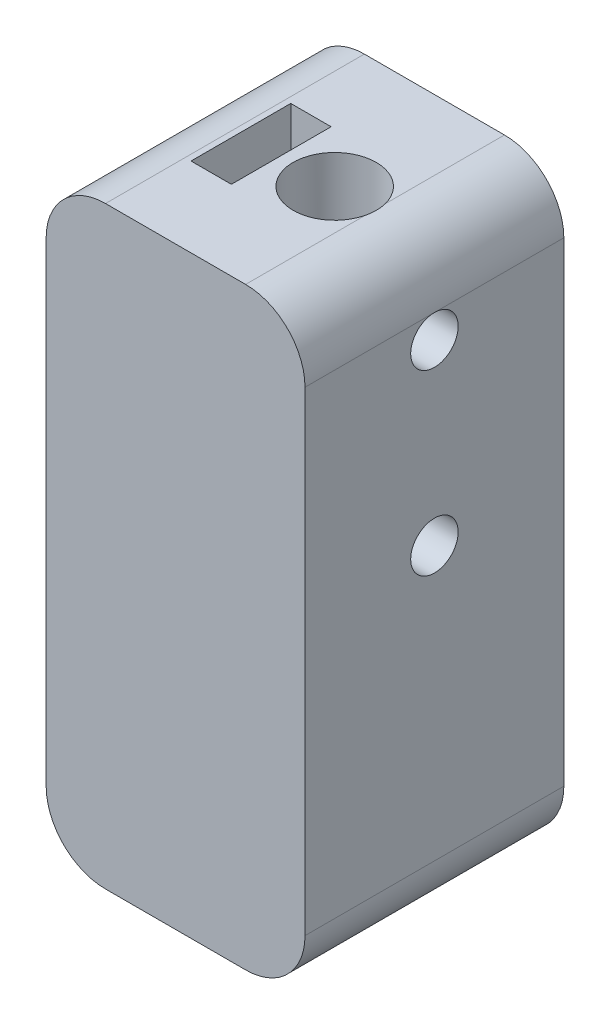
SolidWorks part; units mm, degrees
ref_plane "Alzado" through (0, 0, 0) normal (0, 0, 1) x (1, 0, 0)
ref_plane "Planta" through (0, 0, 0) normal (0, 1, 0) x (1, 0, 0)
ref_plane "Vista lateral" through (0, 0, 0) normal (1, 0, 0) x (0, 0, -1)
sketch "Croquis1" plane through (0, 0, 0) normal (1, 0, 0) x (0, 0, -1)
  line L1 (0, 0) -> (-21.8, 0)
  line L2 (0, 0) -> (0, -50)
  line L3 (0, -50) -> (-21.8, -50)
  line L4 (-21.8, 0) -> (-21.8, -50)
  dimension "D1" = 21.8
  dimension "D2" = 50
extrude "Saliente-Extruir1" add sketch "Croquis1" along normal blind 21.8 contours L2 L3 L4 L1
sketch "Croquis6" plane through (0, 0, 0) normal (-1, 0, 0) x (0, 0, 1)
  line L1 (10.9, -7) -> (10.9, 0) construction
  line L2 (10.9, -22) -> (10.9, -7) construction
  line L3 (0, 0) -> (21.8, 0) construction
  circle A0 centre (10.9, -22) radius 2
  circle A1 centre (10.9, -7) radius 2
  dimension "D1" = 15
  dimension "D3" = 4
  dimension "D4" = 4
  dimension "D2" = 7
extrude "Cortar-Extruir2" cut sketch "Croquis6" against normal up to surface (21.8 mm away) up to face at (21.8, -25, 10.9)
sketch "Croquis7" plane through (21.8, 0, 0) normal (1, 0, 0) x (0, 0, -1)
  line L2 (-10.9, -22) -> (-10.9, -7) construction
  circle A0 centre (-10.9, -22) radius 3.5
  circle A1 centre (-10.9, -7) radius 3.5
  circle A2 centre (-10.9, -7) radius 2 construction
  dimension "D1" = 7
  dimension "D2" = 7
  dimension "D3" = 15
sketch "Croquis11" plane through (0, -50, 0) normal (0, -1, 0) x (1, 0, 0)
  line L0 (13.4, 5.9) -> (13.4, 10.9) construction
  line L1 (0, 0) -> (0, 21.8) construction
  line L2 (0, 0) -> (0, 21.8) construction
  line L7 (16.9, 10.9) -> (21.8, 10.9) construction
  line L8 (13.4, 10.9) -> (8.9, 10.9) construction
  line L9 (8.9, 15.1) -> (5.5, 15.1)
  line L14 (8.9, 15.1) -> (8.9, 6.7)
  line L16 (8.9, 6.7) -> (5.5, 6.7)
  line L17 (5.5, 15.1) -> (5.5, 6.7)
  line L18 (21.8, 0) -> (21.8, 21.8) construction
  line L19 (5.5, 10.9) -> (0, 10.9) construction
  circle A1 centre (13.4, 10.9) radius 3.5
  dimension "D1" = 8.4
  dimension "D2" = 5.5
  dimension "D3" = 5
  dimension "D4" = 3.4
  dimension "D5" = 4.5
extrude "Cortar-Extruir4" cut sketch "Croquis11" against normal up to next
fillet "Redondeo1" radius 5 4 edges at (21.8, -50, 10.9) (0, -50, 10.9) (21.8, 0, 10.9) (0, 0, 10.9)
sketch "Croquis13" plane through (0, 0, 0) normal (-1, 0, 0) x (0, 0, 1)
  line L0 (10.9, -7) -> (10.9, -22) construction
  line L1 (10.9, -14.5) -> (2.8317, -14.5) construction
  circle A0 centre (10.9, -22) radius 2 construction
  circle A1 centre (10.9, -7) radius 2 construction
  circle A2 centre (10.9, -22) radius 2 construction
  circle A3 centre (10.9, -7) radius 2 construction
  circle A4 centre (10.9, -7) radius 3.5
  circle A5 centre (10.9, -22) radius 3.5
  dimension "D1" = 7
extrude "Cortar-Extruir6" cut sketch "Croquis13" against normal blind 3.5
sketch "Croquis15" plane through (0, -50, 0) normal (0, -1, 0) x (1, 0, 0)
  line L0 (5.5, 6.7) -> (8.9, 6.7) construction
  line L1 (8.9, 6.7) -> (8.9, 15.1) construction
  line L2 (8.9, 15.1) -> (5.5, 15.1) construction
  line L3 (5.5, 15.1) -> (5.5, 6.7) construction
  line L4 (5.5, 6.7) -> (8.9, 6.7)
  line L5 (8.9, 6.7) -> (8.9, 15.1)
  line L6 (8.9, 15.1) -> (5.5, 15.1)
  line L7 (5.5, 15.1) -> (5.5, 6.7)
  arc A0 (16.8, 10.0693) -> (16.8, 11.7307) centre (13.4, 10.9) ccw construction
  arc A1 (16.8, 11.7307) -> (16.8, 10.0693) centre (13.4, 10.9) ccw construction
  arc A2 (16.8, 10.0693) -> (16.8, 11.7307) centre (13.4, 10.9) ccw
  arc A3 (16.8, 11.7307) -> (16.8, 10.0693) centre (13.4, 10.9) ccw
extrude "Saliente-Extruir2" add sketch "Croquis15" against normal blind 13
